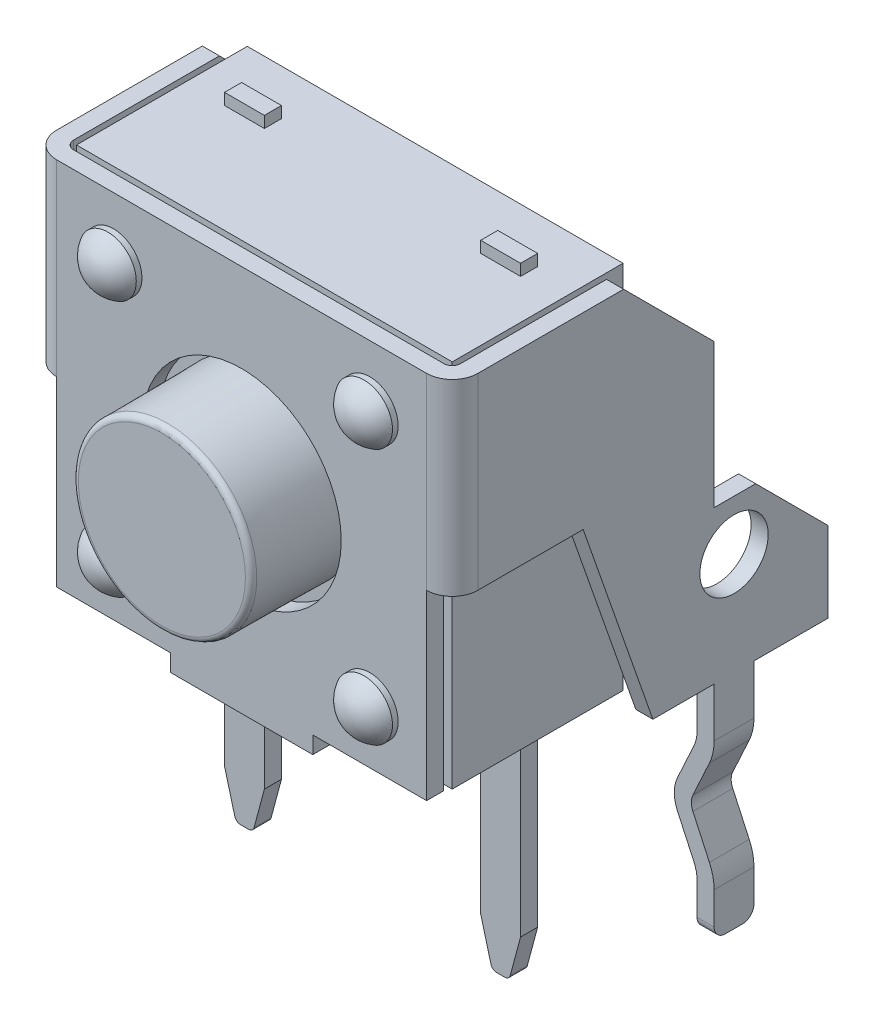
SolidWorks part; units mm, degrees
material "Nickel"
ref_plane "Front Plane" through (0, 0, 0) normal (0, 0, 1) x (1, 0, 0)
ref_plane "Top Plane" through (0, 0, 0) normal (0, 1, 0) x (1, 0, 0)
ref_plane "Right Plane" through (0, 0, 0) normal (1, 0, 0) x (0, 0, -1)
ref_plane "Plane1" through (0, 2, 0) normal (0, 1, 0) x (-1, 0, 0)
sketch "Sketch1" plane through (0, 2, 0) normal (0, 1, 0) x (-1, 0, 0)
  line L0 (-3.7, 1.65) -> (-3.7, -4.5)
  line L1 (-3.25, -4.95) -> (3.25, -4.95)
  line L2 (3.7, -4.5) -> (3.7, 1.65)
  arc A0 (-3.7, -4.5) -> (-3.25, -4.95) centre (-3.25, -4.5) ccw
  arc A1 (3.25, -4.95) -> (3.7, -4.5) centre (3.25, -4.5) ccw
  point P3 (0, -4.95)
  point P8 (-3.7, -4.95)
  point P11 (3.7, -4.95)
  dimension "D4" = 0.45
  dimension "D1" = 6.6
  dimension "D2" = 7.4
  dimension "D3" = 4.95
extrude "Extrude-Thin1" add sketch "Sketch1" along normal blind 6.8 thin thin type one direction reverse wall 0.3
sketch "Sketch2" plane through (-3.7, 0, 0) normal (-1, 0, 0) x (0, 0, 1)
  line L0 (-4.65, 2) -> (-4.65, 5.5)
  line L1 (-4.65, 5.5) -> (-2.65, 5.5)
  line L2 (-2.65, 5.5) -> (-1.425, 2)
  line L3 (-4.5, 2) -> (1.65, 2) construction
  line L4 (-1.425, 2) -> (-4.65, 2)
  line L5 (-1.9395, 8.8) -> (-0.35, 7.2105)
  line L6 (-4.5, 8.8) -> (1.65, 8.8) construction
  line L7 (1.65, 8.8) -> (1.65, 2) construction
  line L8 (1.65, 3.4122) -> (1.65, 8.8)
  line L9 (1.65, 8.8) -> (-1.9395, 8.8)
  line L10 (-0.35, 7.2105) -> (-0.35, 4.6822)
  line L11 (-0.35, 4.6822) -> (0.38, 4.6822)
  line L12 (0.38, 4.6822) -> (1.65, 3.4122)
  line L13 (-4.5, 2) -> (1.65, 2) construction
  line L14 (-4.65, 8.8) -> (-4.65, 2) construction
  circle A0 centre (0, 3.8) radius 0.6
  dimension "D5" = 1.2
  dimension "D1" = 3.5
  dimension "D2" = 2
  dimension "D3" = 3.225
  dimension "D4" = 45
  dimension "D6" = 1.8
  dimension "D7" = 2
extrude "Cut-Extrude1" cut sketch "Sketch2" against normal through all
sketch "Sketch3" plane through (0, 0, -4.95) normal (0, 0, -1) x (-1, 0, 0)
  line L0 (-3.6743, 2) -> (3.6743, 2) construction
  line L1 (3.7, 5.5) -> (3.25, 5.5)
  line L2 (3.7, 5.5) -> (3.7, 2)
  line L3 (3.7, 2) -> (1.25, 2)
  line L4 (3.25, 5.5) -> (3.25, 2.3)
  line L5 (-3.25, 2) -> (3.25, 2) construction
  line L6 (-3.7, 5.5) -> (-3.25, 5.5)
  line L7 (-3.7, 5.5) -> (-3.7, 2)
  line L8 (-3.7, 2) -> (-1.25, 2)
  line L9 (-3.25, 5.5) -> (-3.25, 2.3)
  line L12 (-3.25, 2.3) -> (-1.25, 2.3)
  line L13 (-1.25, 2) -> (-1.25, 2.3)
  line L16 (3.25, 2.3) -> (1.25, 2.3)
  line L17 (1.25, 2) -> (1.25, 2.3)
  circle A0 centre (0, 5.5) radius 1.75
  dimension "D2" = 3.5
  dimension "D1" = 0.45
  dimension "D3" = 2
  dimension "D4" = 0.3
extrude "Cut-Extrude2" cut sketch "Sketch3" against normal up to surface (0.3 mm away)
sketch "Sketch5" plane through (0, 0, 0) normal (0, 0, 1) x (1, 0, 0)
  line L0 (-3.4, 2) -> (-3.4, 1.1315)
  line L1 (-3.345, 0.8805) -> (-3.055, 0.251)
  line L2 (-3.055, -0.251) -> (-3.345, -0.8805)
  line L3 (-3.4, -1.1315) -> (-3.4, -1.9)
  arc A0 (-3.055, 0.251) -> (-3.055, -0.251) centre (-3.6, 0) cw
  arc A1 (-3.4, 1.1315) -> (-3.345, 0.8805) centre (-2.8, 1.1315) ccw
  arc A2 (-3.345, -0.8805) -> (-3.4, -1.1315) centre (-2.8, -1.1315) ccw
  point P10 (-2.9394, 0)
  point P13 (-3.4, 1)
  point P16 (-3.4, -1)
  point P17 (-3, 0)
  dimension "D5" = 0.6
  dimension "D1" = 2
  dimension "D2" = 3.9
  dimension "D3" = 3
  dimension "D4" = 2
extrude "Extrude-Thin2" add sketch "Sketch5" along normal mid plane 0.7 thin thin type one direction wall 0.3
fillet "Fillet1" radius 0.2 2 edges at (-3.55, -1.9, 0.35) (-3.55, -1.9, -0.35)
sketch "Sketch6" plane through (0, 0, -4.95) normal (0, 0, -1) x (-1, 0, 0)
  circle A2 centre (-2.25, 3.25) radius 0.5
  circle A4 centre (0, 5.5) radius 1.75 construction
  dimension "D1" = 1
  dimension "D3" = 2.25
  dimension "D4" = 2.25
extrude "Extrude1" add sketch "Sketch6" along normal blind 0.1
dome "Dome1" faces to dome 1 distance 0.3 reverse direction no elliptical dome no face at (1.75, 3.25, -5.05) parameters "D1"=0.3
pattern_linear "LPattern1" count 2 spacing 4.5 along (0, 1, 0) count 2 spacing 4.5 along (-1, 0, 0) of "Extrude1", "Dome1"
sketch "Sketch7" plane through (0, 8.8, 0) normal (0, 1, 0) x (-1, 0, 0)
  line L1 (3.4, -4.5) -> (3.4, -1.9395) construction
  line L2 (3.3, -4.55) -> (-3.3, -4.55)
  line L3 (3.3, -4.55) -> (3.3, -1.55)
  line L4 (3.3, -1.55) -> (-3.3, -1.55)
  line L6 (-3.3, -4.55) -> (-3.3, -1.55)
  line L7 (-3.25, -4.65) -> (3.25, -4.65) construction
  line L8 (-3.4, -2.65) -> (-3.4, -4.5) construction
  point P4 (3.4, -3.2198)
  point P9 (-3.4, -3.575)
  dimension "D1" = 0.1
  dimension "D2" = 0.1
  dimension "D3" = 0.1
  dimension "D4" = 3
extrude "Extrude2" add sketch "Sketch7" against normal up to surface (6.5 mm away) up to face at (-2.25, 2.3, -4.8)
ref_plane "Plane2" through (0, 0, -5.65) normal (0, 0, -1) x (-1, 0, 0)
sketch "Sketch8" plane through (0, 0, 0) normal (0, 0, -1) x (-1, 0, 0)
  circle A0 centre (0, 5.5) radius 1.6
  dimension "D1" = 3.2
extrude "Extrude3" add sketch "Sketch8" along normal blind 3.85 draft 0.5 from offset 2.5
fillet "Fillet2" radius 0.1 1 edges at (-1.5664, 5.5, -6.35)
ref_plane "Plane3" through (0, 0, -2.5) normal (0, 0, -1) x (-1, 0, 0)
sketch "Sketch9" plane through (0, 0, -2.5) normal (0, 0, -1) x (-1, 0, 0)
  line L1 (2.6, 9) -> (1.9, 9)
  line L2 (1.9, 9) -> (1.9, -1.25)
  line L3 (2.101, -2) -> (2.399, -2)
  line L4 (2.6, 9) -> (2.6, -1.25)
  line L5 (2.6, -1.25) -> (2.399, -2)
  line L6 (2.101, -2) -> (1.9, -1.25)
  line L7 (3.4, -1.9) -> (3.7, -1.9) construction
  line L8 (-3.25, 8.8) -> (3.25, 8.8) construction
  point P2 (2.25, -2)
  dimension "D1" = 2.25
  dimension "D2" = 0.7
  dimension "D3" = 75
  dimension "D4" = 75
  dimension "D5" = 0.75
  dimension "D6" = 0.1
  dimension "D7" = 0.2
extrude "Extrude4" add sketch "Sketch9" along normal mid plane 0.3
fillet "Fillet3" radius 0.1 2 edges at (-2.101, -2, -2.5) (-2.399, -2, -2.5)
mirror "Mirror1" about plane through (0, 0, 0) normal (1, 0, 0) of "Fillet1", "Extrude-Thin2"
mirror "Mirror2" about plane through (0, 0, 0) normal (1, 0, 0) of "Fillet3", "Extrude4"
sketch "Sketch10" plane through (0, 0, -4.55) normal (0, 0, -1) x (-1, 0, 0)
  circle A3 centre (-2.25, 7.75) radius 0.4
  circle A4 centre (-2.25, 7.75) radius 0.4
  circle A6 centre (2.25, 7.75) radius 0.4
  circle A7 centre (2.25, 7.75) radius 0.4
  circle A9 centre (-2.25, 3.25) radius 0.4
  circle A10 centre (-2.25, 3.25) radius 0.4
  circle A12 centre (2.25, 3.25) radius 0.4
  circle A13 centre (2.25, 3.25) radius 0.4
  dimension "D1" = 0.1
  dimension "D2" = 0.1
  dimension "D3" = 0.1
  dimension "D4" = 0.1
extrude "Extrude5" add sketch "Sketch10" along normal up to surface (0.1 mm away)
move or copy body "Body-Move/Copy1" bodies to move or copy 112 copy no rotation origin (0, 0, 0) rotation axis (0, 1, 0) rotation angle 180
move or copy body "Body-Move/Copy2" bodies to move or copy 113 copy no translate (0, -2, 0)
